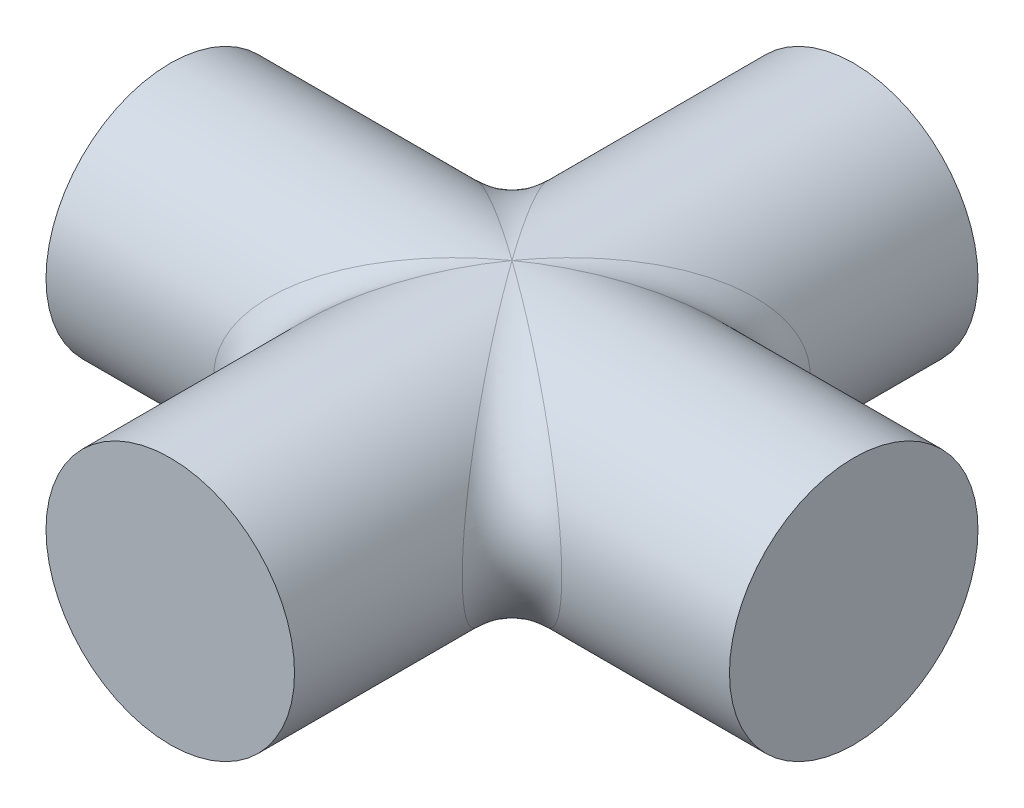
SolidWorks part; units mm, degrees
ref_plane "Front Plane" through (0, 0, 0) normal (0, 0, 1) x (1, 0, 0)
ref_plane "Top Plane" through (0, 0, 0) normal (0, 1, 0) x (1, 0, 0)
ref_plane "Right Plane" through (0, 0, 0) normal (1, 0, 0) x (0, 0, -1)
sketch "Sketch1" plane through (0, 0, 0) normal (0, 0, 1) x (1, 0, 0)
  circle A0 centre (0, 0) radius 6.35
  dimension "D1" = 12.7
extrude "Boss-Extrude1" add sketch "Sketch1" along normal mid plane 34.925
sketch "Sketch2" plane through (0, 0, 0) normal (1, 0, 0) x (0, 0, -1)
  circle A0 centre (0, 0) radius 6.35
  dimension "D1" = 12.7
extrude "Boss-Extrude2" add sketch "Sketch2" along normal mid plane 34.925
fillet "Fillet1" radius 2.54 4 edges at (-6.35, 0, -6.35) (6.35, 0, 6.35) (-6.35, 0, 6.35) (6.35, 0, -6.35)
